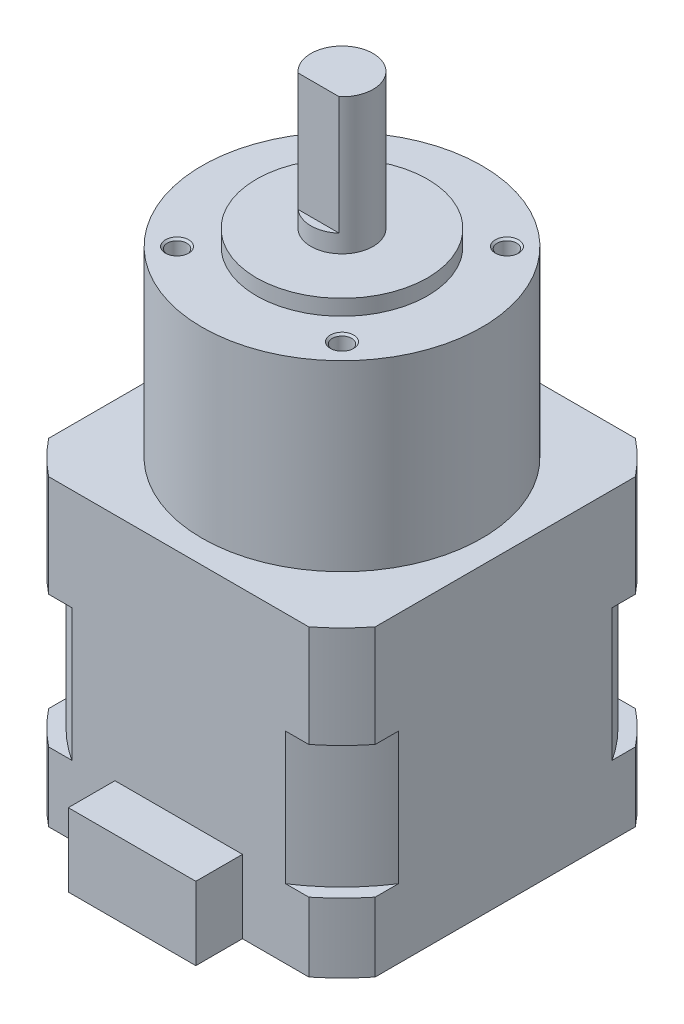
SolidWorks part; units mm, degrees
material "3.0505 (EN-AW 3105)"
ref_plane "Płaszczyzna przednia" through (0, 0, 0) normal (0, 0, 1) x (1, 0, 0)
ref_plane "Płaszczyzna górna" through (0, 0, 0) normal (0, 1, 0) x (1, 0, 0)
ref_plane "Płaszczyzna prawa" through (0, 0, 0) normal (1, 0, 0) x (0, 0, -1)
sketch "Szkic1" plane through (0, 0, 0) normal (0, 1, 0) x (1, 0, 0)
  line L0 (-2.6458, -3) -> (2.6458, -3)
  line L1 (-21, -21) -> (21, -21)
  line L2 (-21, -21) -> (-21, 21)
  line L3 (-21, 21) -> (21, 21)
  line L4 (21, -21) -> (21, 21)
  line L5 (-21, -21) -> (21, 21) construction
  line L6 (-21, 21) -> (21, -21) construction
  line L7 (0, 0) -> (0, 5.9906) construction
  circle A0 centre (0, 0) radius 18
  circle A1 centre (0, 0) radius 11
  circle A2 centre (0, 0) radius 4
  arc A3 (-2.6458, -3) -> (2.6458, -3) centre (0, 0) cw
  point P0 (0, 0)
  point P14 (0, 4)
  point P16 (0, 0)
  point P17 (0, 0)
  dimension "D2" = 36
  dimension "D3" = 22
  dimension "D4" = 8
  dimension "D1" = 42
  dimension "D5" = 7
extrude "Dodanie-wyciągnięcie1" add sketch "Szkic1" along normal blind 39 contours L4 L3 L2 L1
extrude "Dodanie-wyciągnięcie2" add sketch "Szkic1<3>" along normal blind 62.5 contours A0
sketch "Szkic1<3>" plane through (0, 0, 0) normal (0, 1, 0) x (1, 0, 0) same geometry as "Szkic1"
extrude "Dodanie-wyciągnięcie3" add sketch "Szkic1<4>" along normal blind 64.5 contours A1
sketch "Szkic1<4>" plane through (0, 0, 0) normal (0, 1, 0) x (1, 0, 0) same geometry as "Szkic1"
extrude "Dodanie-wyciągnięcie4" add sketch "Szkic1<5>" along normal blind 66.8 contours A2
sketch "Szkic1<5>" plane through (0, 0, 0) normal (0, 1, 0) x (1, 0, 0) same geometry as "Szkic1"
extrude "Dodanie-wyciągnięcie5" add sketch "Szkic1<6>" along normal blind 82 contours L0 A3
sketch "Szkic1<6>" plane through (0, 0, 0) normal (0, 1, 0) x (1, 0, 0) same geometry as "Szkic1"
sketch "Szkic2" plane through (0, 0, 0) normal (0, 1, 0) x (1, 0, 0)
  circle A0 centre (0, 0) radius 26.85
  dimension "D1" = 53.7
extrude "Wytnij-wyciągnięcie2" cut sketch "Szkic2" along normal through all flip side to cut
sketch "Szkic3" plane through (0, 0, 0) normal (0, 1, 0) x (1, 0, 0)
  circle A0 centre (0, 0) radius 25.1
  dimension "D1" = 50.2
extrude "Wytnij-wyciągnięcie3" cut sketch "Szkic3" along normal blind 17 from offset 8.9 flip side to cut
sketch "Szkic4" plane through (0, 0, 0) normal (0, 1, 0) x (1, 0, 0)
  circle A0 centre (0, 0) radius 4.65
  dimension "D1" = 9.3
extrude "Wytnij-wyciągnięcie5" cut sketch "Szkic4" along normal blind 4
sketch "Szkic5" plane through (0, 0, 0) normal (0, 1, 0) x (1, 0, 0)
  line L0 (0, 0) -> (-21.8173, 21.8173) construction
  line L1 (0, 0) -> (17.0567, 17.0567) construction
  line L2 (-16.7309, 21) -> (16.7309, 21) construction
  circle A0 centre (0, 0) radius 15 construction
  point P4 (-10.6066, 10.6066)
  point P8 (10.6066, 10.6066)
  point P9 (10.6066, -10.6066)
  point P10 (-10.6066, -10.6066)
  dimension "D1" = 30
  dimension "D2" = 45
hole_wizard "Otwór gwintowany M31" positions "Szkic6" profile "Szkic8" hole size "M3" standard "ISO"
sketch "Szkic6" plane through (0, 62.5, 0) normal (0, 1, 0) x (1, 0, 0)
  point P0 (-10.6066, 10.6066)
  point P3 (10.6066, 10.6066)
  point P6 (10.6066, -10.6066)
  point P9 (-10.6066, -10.6066)
sketch "Szkic8" plane through (-10.6066, 62.5, -10.6066) normal (1, 0, 0) x (0, 0, 1)
  line L0 (0, 0) -> (0, 9.7511)
  line L1 (0, 9.7511) -> (1.25, 9)
  line L2 (1.25, 9) -> (1.25, 0.25)
  line L3 (1.25, 0.25) -> (1.5, 0)
  line L5 (1.5, 0) -> (0, 0)
  line L6 (-1.25, 0.25) -> (-1.5, 0) construction
  line L10 (0, 9.7511) -> (-1.25, 9) construction
  line L11 (0, -6.35) -> (0, 107.95) construction
  dimension "Średnica otworu" = 2.5
  dimension "Głębokośc otworu" = 9
  dimension "Średnica zewnętrznego pogłębienia stożkowego" = 3
  dimension "Kąt zewnętrznego pogłębienia stożkowego" = 90
  dimension "Kąt wiertła" = 118
sketch "Szkic18" plane through (0, 0, 0) normal (0, 0, 1) x (1, 0, 0)
  line L0 (15, 0) -> (-15, 0) construction
  line L1 (-8.2, 0) -> (8.2, 0)
  line L2 (-8.2, 0) -> (-8.2, 9.4)
  line L3 (-8.2, 9.4) -> (8.2, 9.4)
  line L4 (8.2, 0) -> (8.2, 9.4)
  dimension "D1" = 9.4
  dimension "D2" = 16.4
  dimension "D3" = 8.2
extrude "Dodanie-wyciągnięcie6" add sketch "Szkic18" along normal blind 6 from surface starting at face at (0, 18.1, 21)
equation "\"D3@Szkic18\"=\"D2@Szkic18\"/2"
